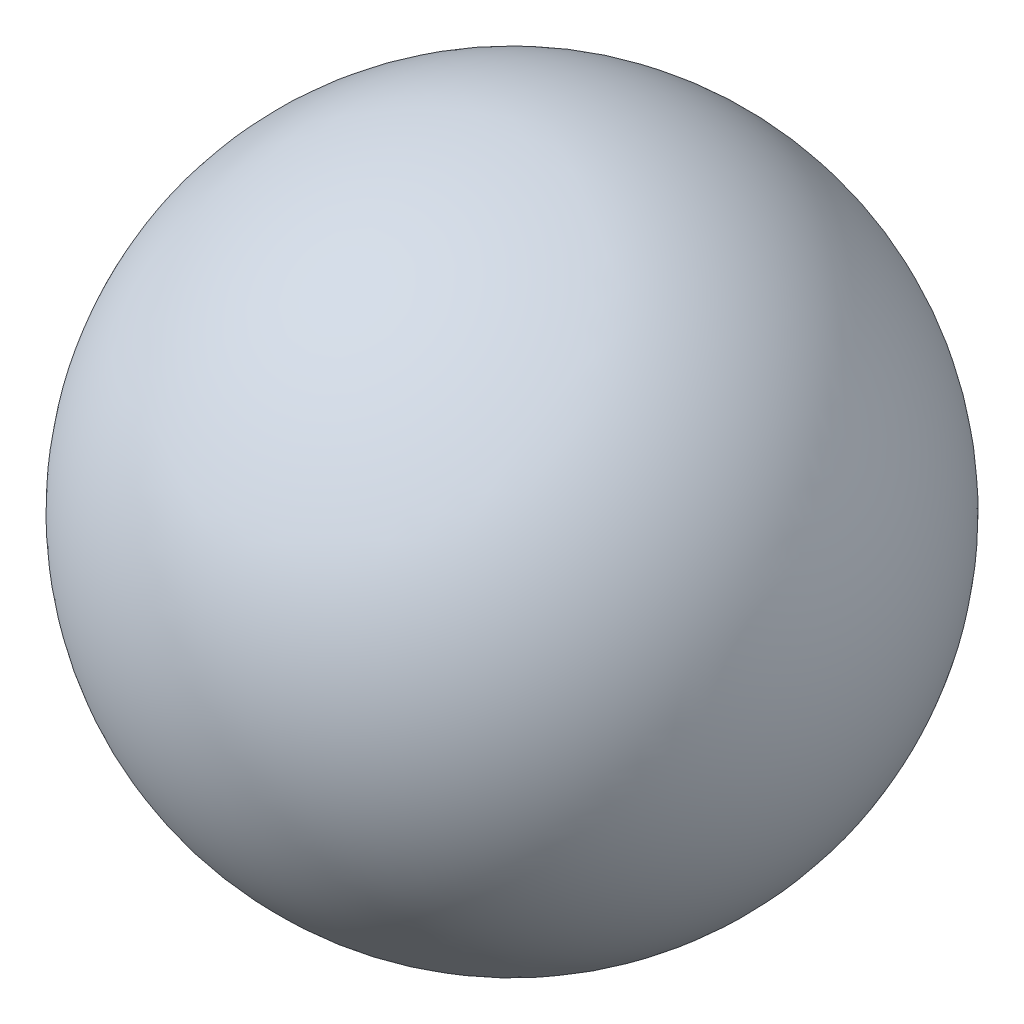
SolidWorks part; units mm, degrees
ref_plane "Front Plane" through (0, 0, 0) normal (0, 0, 1) x (1, 0, 0)
ref_plane "Top Plane" through (0, 0, 0) normal (0, 1, 0) x (1, 0, 0)
ref_plane "Right Plane" through (0, 0, 0) normal (1, 0, 0) x (0, 0, -1)
sketch "Sketch1" plane through (0, 0, 0) normal (0, 1, 0) x (1, 0, 0)
  line L0 (-1.48, 0) -> (1.48, 0) construction
  line L1 (-1.48, 0) -> (1.48, 0)
  circle A0 centre (0, 0) radius 1.48
  dimension "D1" = 2.96
revolve "Revolve1" add sketch "Sketch1" angle 360 about L1 region at (0, 0, -0.6281)
equation "\"bearing_21_OD\"= 21mm"
equation "\"pin_cirlce_diameter\"= 75mm"
equation "\"pin_diam\"= 6mm"
equation "\"gear_thickness\"= 4mm"
equation "\"ball_bearing_diam\"= 2.96mm"
equation "\"bearing_21_outer_clearance\"= 0mm'change this"
equation "\"bearing_15_OD\"= 15mm"
equation "\"bearing_15_outer_clearance\"= 0mm'change this"
equation "\"thrust_bearing_thickness\"= 5mm'measure this irl and change"
equation "\"D1@Sketch1\"=\"ball_bearing_diam\""
